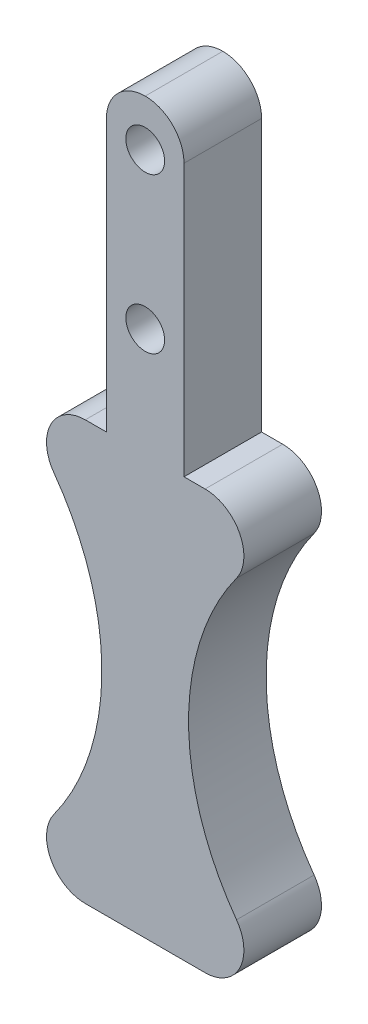
SolidWorks part; units mm, degrees
ref_plane "Front" through (0, 0, 0) normal (0, 0, 1) x (1, 0, 0)
ref_plane "Top" through (0, 0, 0) normal (0, 1, 0) x (1, 0, 0)
ref_plane "Right" through (0, 0, 0) normal (1, 0, 0) x (0, 0, -1)
sketch "Esquisse1" plane through (0, 0, 0) normal (0, 0, 1) x (1, 0, 0)
  line L1 (0, 0) -> (10, 0)
  line L2 (0, 0) -> (0, 94)
  line L3 (0, 94) -> (10, 94)
  line L4 (10, 0) -> (10, 94)
  dimension "D1" = 10
  dimension "D2" = 94
extrude "Boss.-Extru.1" add sketch "Esquisse1" along normal blind 10
sketch "Esquisse2" plane through (0, 0, 10) normal (0, 0, 1) x (1, 0, 0)
  line L0 (5, 94) -> (5, 68) construction
  line L1 (10, 94) -> (0, 94) construction
  circle A0 centre (5, 68) radius 2.5
  circle A1 centre (5, 88) radius 2.5
  dimension "D1" = 20
  dimension "D2" = 6
  dimension "D3" = 5
extrude "Enlèv. mat.-Extru.1" cut sketch "Esquisse2" against normal up to vertex (10 mm away) up to point (0, 94, 0)
fillet "Congé1" radius 5 2 edges at (10, 94, 5) (0, 94, 5)
sketch "Esquisse3" plane through (0, 0, 10) normal (0, 0, 1) x (1, 0, 0)
  line L0 (0, 0) -> (0, 54)
  line L1 (0, 89) -> (0, 0) construction
  line L2 (0, 54) -> (-15, 54)
  line L3 (-15, 0) -> (0, 0)
  line L4 (-15, 54) -> (-15, 0) construction
  line L5 (5, 0) -> (5, 34.4675) construction
  line L6 (0, 0) -> (10, 0) construction
  line L7 (25, 54) -> (25, 0) construction
  line L8 (25, 0) -> (10, 0)
  line L9 (10, 54) -> (25, 54)
  line L10 (10, 0) -> (10, 54)
  arc A0 (-15, 54) -> (-15, 0) centre (-33.0901, 27) cw
  arc A1 (25, 54) -> (25, 0) centre (43.0901, 27) ccw
  dimension "D1" = 32.5
  dimension "D2" = 15
  dimension "D3" = 54
extrude "Boss.-Extru.2" add sketch "Esquisse3" against normal up to vertex (10 mm away) up to point (10, 0, 0)
fillet "Congé2" radius 5 4 edges at (25, 0, 5) (25, 54, 5) (-15, 54, 5) (-15, 0, 5)
